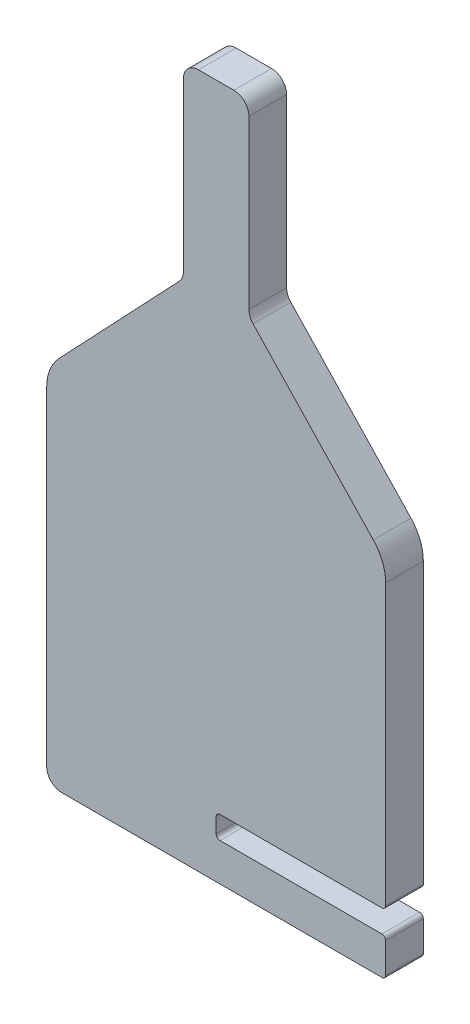
SolidWorks part; units mm, degrees
ref_plane "Alzado" through (0, 0, 0) normal (0, 0, 1) x (1, 0, 0)
ref_plane "Planta" through (0, 0, 0) normal (0, 1, 0) x (1, 0, 0)
ref_plane "Vista lateral" through (0, 0, 0) normal (1, 0, 0) x (0, 0, -1)
sketch "Croquis1" plane through (0, 0, 0) normal (0, 0, 1) x (1, 0, 0)
  line L0 (-4.35, 20) -> (-22.5, 0.8287)
  line L1 (-4.35, 45) -> (4.35, 45)
  line L2 (-22.5, 0.8287) -> (-22.5, -47.1713)
  line L3 (-22.5, -47.1713) -> (22.5, -47.1713)
  line L4 (22.5, 0.8287) -> (22.5, -47.1713)
  line L5 (-4.35, 45) -> (4.35, 45)
  line L6 (-4.35, 45) -> (-4.35, 20)
  line L8 (4.35, 45) -> (4.35, 19.999)
  line L9 (4.35, 19.999) -> (22.5, 0.8287)
  line L10 (0, 72.8664) -> (0, -82.626) construction
  dimension "D1" = 45
  dimension "D2" = 25
  dimension "D3" = 4.35
  dimension "D4" = 22.5
  dimension "D5" = 45
  dimension "D6" = 4.35
  dimension "D7" = 26.3993
  dimension "D8" = 26.4
  dimension "D9" = 48
  dimension "D10" = 48
extrude "Saliente-Extruir1" add sketch "Croquis1" along normal blind 5 contours L6 L0 L2 L3 L4 L9 L8 L1
sketch "Croquis3" plane through (0, 0, 5) normal (0, 0, 1) x (1, 0, 0)
  line L0 (22.5, 0.8287) -> (22.5, -47.1713) construction
  line L1 (22.5, -39.1713) -> (0, -39.1713)
  line L2 (22.5, -39.1713) -> (22.5, -42.1713)
  line L3 (22.5, -42.1713) -> (0, -42.1713)
  line L4 (0, -39.1713) -> (0, -42.1713)
  line L5 (-22.5, -47.1713) -> (22.5, -47.1713) construction
  dimension "D1" = 3
  dimension "D2" = 5
  dimension "D3" = 22.5
extrude "Cortar-Extruir2" cut sketch "Croquis3" against normal up to surface (5 mm away) up to face at (0, 4.6642, 0)
fillet "Redondeo1" radius 2 5 edges at (-22.5, -47.1713, 2.5) (-4.35, 20, 2.5) (-4.35, 45, 2.5) (4.35, 19.999, 2.5) (4.35, 45, 2.5)
fillet "Redondeo2" radius 6 2 edges at (-22.5, 0.8287, 2.5) (22.5, 0.8287, 2.5)
fillet "Redondeo3" radius 0.5 5 edges at (0, -42.1713, 2.5) (0, -39.1713, 2.5) (22.5, -42.1713, 2.5) (22.5, -39.1713, 2.5) (22.5, -47.1713, 2.5)
